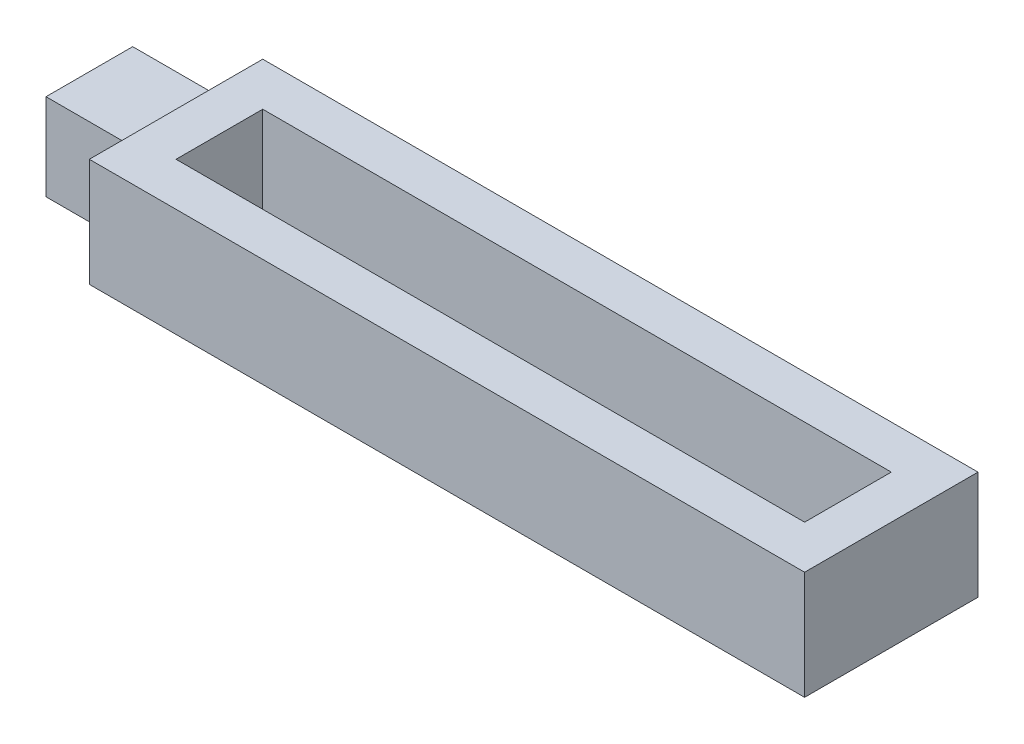
SolidWorks part; units mm, degrees
ref_plane "Front Plane" through (0, 0, 0) normal (0, 0, 1) x (1, 0, 0)
ref_plane "Top Plane" through (0, 0, 0) normal (0, 1, 0) x (1, 0, 0)
ref_plane "Right Plane" through (0, 0, 0) normal (1, 0, 0) x (0, 0, -1)
sketch "Sketch1" plane through (0, 0, 0) normal (0, 1, 0) x (1, 0, 0)
  line L0 (-330, 80) -> (-290, 40) construction
  line L1 (-330, 80) -> (330, 80)
  line L2 (-330, 80) -> (-330, -80)
  line L3 (-330, -80) -> (330, -80)
  line L4 (330, 80) -> (330, -80)
  line L5 (-290, -40) -> (290, -40)
  line L6 (-290, -40) -> (-290, 40)
  line L7 (-290, 40) -> (290, 40)
  line L8 (290, -40) -> (290, 40)
  line L9 (-290, -40) -> (290, 40) construction
  line L10 (-290, 40) -> (290, -40) construction
  line L11 (290, 40) -> (330, 80) construction
  line L12 (290, -40) -> (330, -80) construction
  line L13 (-330, -80) -> (-290, -40) construction
  line L14 (-290, -40) -> (-290, -80) construction
  line L15 (-290, -40) -> (-330, -40) construction
  line L16 (-330, -40) -> (-410, -40)
  line L17 (-410, -40) -> (-410, 40)
  line L18 (-410, 40) -> (-330, 40)
  point P4 (0, 0)
  dimension "D1" = 580
  dimension "D2" = 80
  dimension "D3" = 40
  dimension "D4" = 80
extrude "Boss-Extrude1" add sketch "Sketch1" against normal blind 50 and the other way blind 50 contours L4 L1 L2 L3 L8 L5 L6 L7 region at (0, 0, -73.2088)
extrude "Boss-Extrude2" add sketch "Sketch1<3>" along normal blind 40 and the other way blind 40 contours L18 L17 L16 L2 region at (-370, 0, 0)
sketch "Sketch1<3>" plane through (0, 0, 0) normal (0, 1, 0) x (1, 0, 0) same geometry as "Sketch1"
